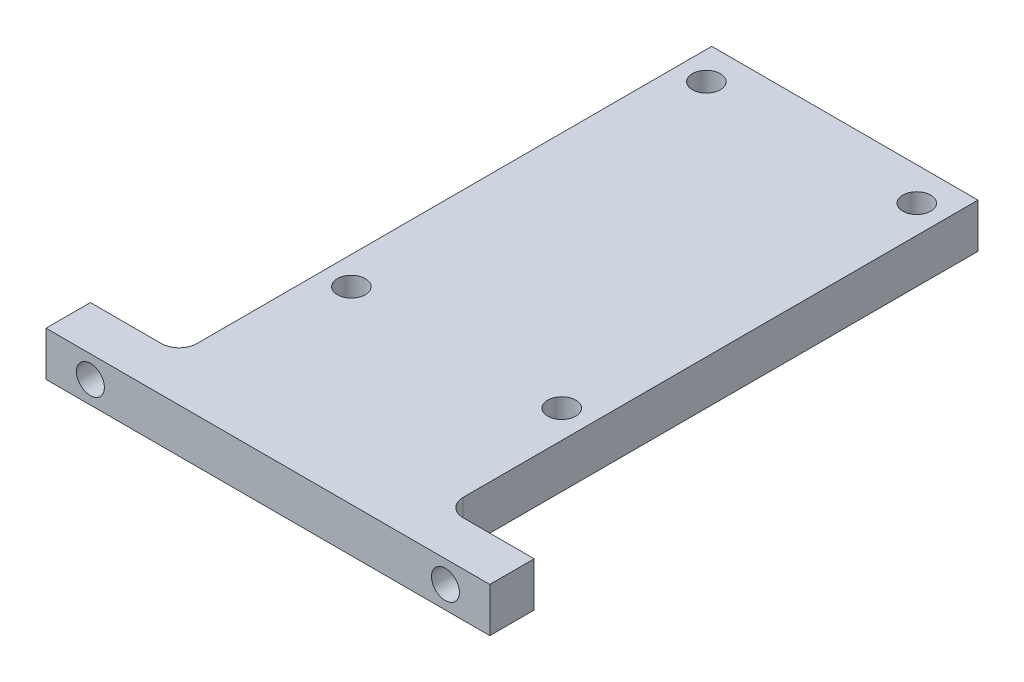
SolidWorks part; units mm, degrees
ref_plane "Front Plane" through (0, 0, 0) normal (0, 0, 1) x (1, 0, 0)
ref_plane "Top Plane" through (0, 0, 0) normal (0, 1, 0) x (1, 0, 0)
ref_plane "Right Plane" through (0, 0, 0) normal (1, 0, 0) x (0, 0, -1)
sketch "Sketch1" plane through (0, 0, 0) normal (0, 1, 0) x (1, 0, 0)
  line L0 (0, 0) -> (63.5, 0)
  line L1 (63.5, 0) -> (63.5, 6.35)
  line L2 (63.5, 6.35) -> (50.8, 6.35)
  line L3 (50.8, 6.35) -> (50.8, 82.55)
  line L4 (50.8, 82.55) -> (12.7, 82.55)
  line L5 (12.7, 82.55) -> (12.7, 6.35)
  line L6 (12.7, 6.35) -> (0, 6.35)
  line L7 (0, 6.35) -> (0, 0)
  dimension "D1" = 12.7
  dimension "D2" = 38.1
  dimension "D3" = 76.2
  dimension "D4" = 6.35
extrude "Boss-Extrude1" add sketch "Sketch1" along normal blind 6.35
sketch "Sketch2" plane through (0, 0, 0) normal (0, 0, 1) x (1, 0, 0)
  line L0 (0, 6.35) -> (0, 0) construction
  line L1 (12.7, 6.35) -> (0, 6.35) construction
  line L2 (63.5, 6.35) -> (50.8, 6.35) construction
  circle A0 centre (6.35, 3.175) radius 2
  circle A1 centre (57.15, 3.175) radius 2
  point P7 (0, 3.175)
  point P11 (6.35, 6.35)
  point P15 (57.15, 6.35)
  dimension "D1" = 4
extrude "Cut-Extrude1" cut sketch "Sketch2" against normal through all both and the other way through all
sketch "Sketch3" plane through (0, 6.35, 0) normal (0, 1, 0) x (1, 0, 0)
  line L0 (50.8, 82.55) -> (12.7, 82.55) construction
  line L1 (50.8, 6.35) -> (50.8, 82.55) construction
  line L2 (12.7, 82.55) -> (12.7, 6.35) construction
  circle A0 centre (46.8, 77.7875) radius 2
  circle A1 centre (16.7, 77.7875) radius 2
  circle A2 centre (16.7, 26.9875) radius 2
  circle A3 centre (46.8, 26.9875) radius 2
  dimension "D1" = 4
  dimension "D2" = 4.7625
  dimension "D3" = 4
  dimension "D4" = 4
  dimension "D5" = 50.8
extrude "Cut-Extrude2" cut sketch "Sketch3" against normal through all both and the other way through all
fillet "Fillet1" radius 2.54 2 edges at (12.7, 3.175, -6.35) (50.8, 3.175, -6.35)
